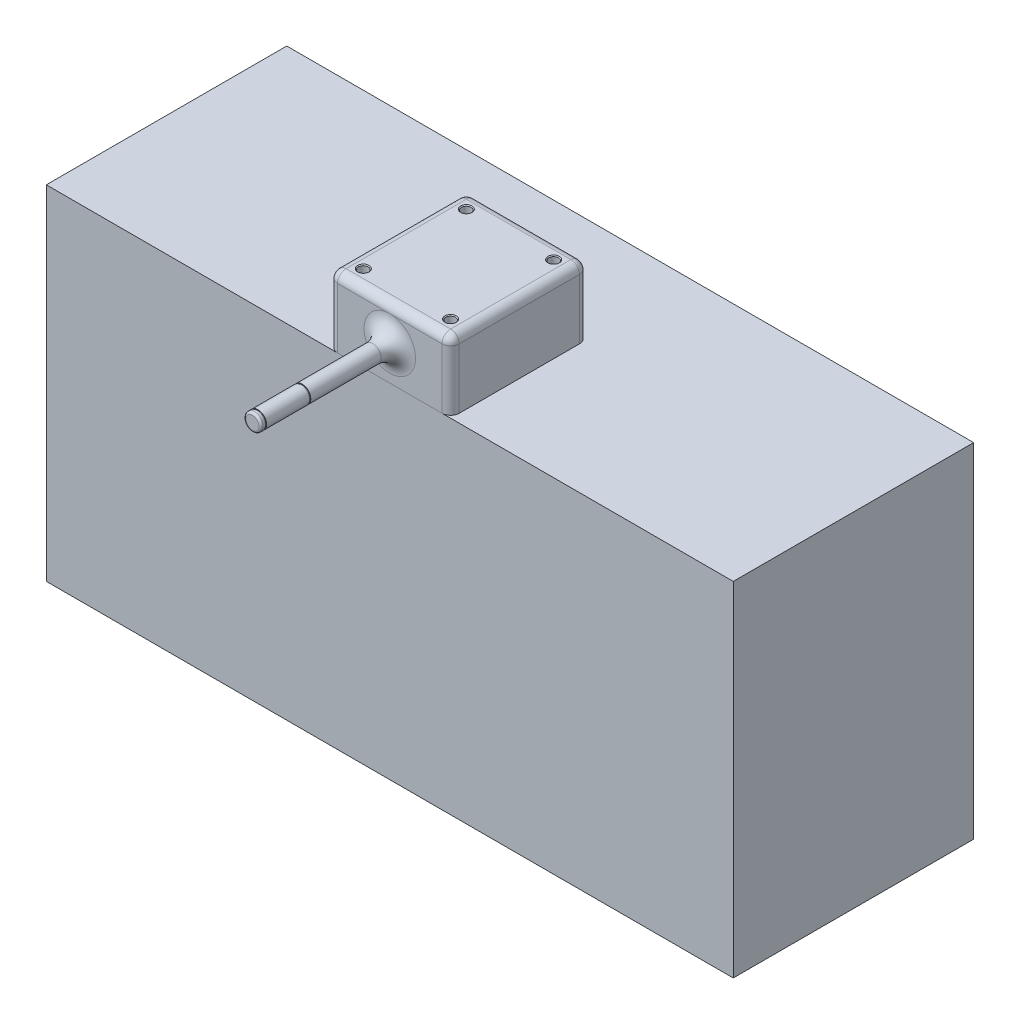
SolidWorks part; units mm, degrees
ref_plane "Front Plane" through (0, 0, 0) normal (0, 0, 1) x (1, 0, 0)
ref_plane "Top Plane" through (0, 0, 0) normal (0, 1, 0) x (1, 0, 0)
ref_plane "Right Plane" through (0, 0, 0) normal (1, 0, 0) x (0, 0, -1)
sketch "Sketch1" plane through (0, 0, 0) normal (0, 0, 1) x (1, 0, 0)
  line L1 (-45, 25.4) -> (45, 25.4)
  line L2 (-45, 25.4) -> (-45, -25.4)
  line L3 (-45, -25.4) -> (45, -25.4)
  line L4 (45, 25.4) -> (45, -25.4)
  line L5 (-45, 25.4) -> (45, -25.4) construction
  line L6 (-45, -25.4) -> (45, 25.4) construction
  circle A0 centre (0, 0) radius 6.35
  point P0 (0, 0)
  dimension "D1" = 12.7
  dimension "D2" = 90
  dimension "D3" = 50.8
extrude "Boss-Extrude1" add sketch "Sketch1" against normal blind 101.6 contours L2 L3 L4 L1
sketch "Sketch10" plane through (0, 0, 0) normal (0, 0, 1) x (1, 0, 0)
  line L0 (-45, -25.4) -> (45, -25.4) construction
  line L1 (-101.6, -25.4) -> (101.6, -25.4)
  line L2 (-101.6, -25.4) -> (-101.6, -228.6)
  line L3 (-101.6, -228.6) -> (101.6, -228.6)
  line L4 (101.6, -25.4) -> (101.6, -228.6)
  point P6 (0, -25.4)
  point P7 (0, -25.4)
  dimension "D1" = 203.2
extrude "Boss-Extrude2" add sketch "Sketch1<3>" along normal blind 101.6 contours A0 region at (0, 0, 0)
sketch "Sketch1<3>" plane through (0, 0, 0) normal (0, 0, 1) x (1, 0, 0) same geometry as "Sketch1"
fillet "Fillet1" radius 6.35 8 edges at (45, 0, 0) (45, 0, -101.6) (-45, 0, -101.6) (-45, 0, 0) (0, 25.4, -101.6) (45, 25.4, -50.8) (0, 25.4, 0) (-45, 25.4, -50.8)
fillet "Fillet2" radius 12.7 1 edges at (6.35, 0, 0)
sketch "Sketch2" plane through (0, 25.4, 0) normal (0, 1, 0) x (1, 0, 0)
  line L0 (-38.65, 50.8) -> (0, 50.8) construction
  line L1 (-32.3, 88.9) -> (32.3, 88.9)
  line L2 (-32.3, 88.9) -> (-32.3, 12.7)
  line L3 (-32.3, 12.7) -> (32.3, 12.7)
  line L4 (32.3, 88.9) -> (32.3, 12.7)
  line L5 (-32.3, 88.9) -> (32.3, 12.7) construction
  line L6 (-32.3, 12.7) -> (32.3, 88.9) construction
  line L7 (-38.65, 95.25) -> (-38.65, 6.35) construction
  line L8 (0, 50.8) -> (0, 6.35) construction
  line L9 (-38.65, 6.35) -> (38.65, 6.35) construction
  line L10 (-32.3, 88.9) -> (-32.3, 95.25) construction
  line L11 (38.65, 95.25) -> (-38.65, 95.25) construction
  line L12 (-32.3, 88.9) -> (-38.65, 88.9) construction
  circle A0 centre (-32.3, 88.9) radius 3.175
  point P0 (0, 50.8)
  dimension "D1" = 6.35
  dimension "D2" = 3.175
hole_wizard "1/4 Clearance Hole1" positions "Sketch3" profile "Sketch4" hole size "1/4" standard "ANSI Inch" end condition through all
sketch "Sketch3" plane through (0, 25.4, 0) normal (0, 1, 0) x (1, 0, 0)
  point P0 (-32.3, 88.9)
  point P3 (-32.3, 12.7)
  point P6 (32.3, 12.7)
  point P9 (32.3, 88.9)
sketch "Sketch4" plane through (-32.3, 25.4, -88.9) normal (1, 0, 0) x (0, 0, 1)
  line L0 (0, 0) -> (0, 50.8)
  line L1 (0, 50.8) -> (3.5687, 50.8)
  line L2 (3.5687, 50.8) -> (3.5687, 0.635)
  line L3 (3.5687, 0.635) -> (4.2037, 0)
  line L5 (4.2037, 0) -> (0, 0)
  line L6 (-3.5687, 0.635) -> (-4.2037, 0) construction
  line L11 (0, -6.35) -> (0, 107.95) construction
  dimension "Thru Hole Dia." = 7.1374
  dimension "Thru Hole Depth" = 50.8
  dimension "Near C'Sink Dia." = 8.4074
  dimension "Near C'Sink Angle" = 90
ref_plane "Plane1" through (0, 6.35, 0) normal (0, 1, 0) x (1, 0, 0)
sketch "Sketch5" plane through (0, 6.35, 0) normal (0, 1, 0) x (1, 0, 0)
  line L0 (-45, -65.7225) -> (45, -65.7225)
  line L1 (-45, -97.4725) -> (45, -97.4725)
  line L2 (-45, -97.4725) -> (-45, -65.7225)
  line L3 (45, -65.7225) -> (45, -97.4725)
  line L4 (-45, -81.5975) -> (0, -81.5975) construction
  line L5 (0, -65.7225) -> (0, -97.4725) construction
  line L6 (0, -101.6) -> (0, -97.4725) construction
  line L7 (-6.35, -101.6) -> (6.35, -101.6) construction
  line L8 (-6.6675, -98.425) -> (0, -97.4725) construction
  line L9 (-6.6675, -97.4725) -> (6.6675, -97.4725)
  line L10 (-6.6675, -97.4725) -> (-6.6675, -98.425)
  line L11 (-6.6675, -98.425) -> (6.6675, -98.425)
  line L12 (6.6675, -97.4725) -> (6.6675, -98.425)
  line L13 (0, -97.4725) -> (6.6675, -98.425) construction
  line L14 (0, -65.7225) -> (6.6675, -64.77) construction
  line L15 (-6.6675, -64.77) -> (0, -65.7225) construction
  line L16 (6.6675, -65.7225) -> (6.6675, -64.77)
  line L17 (-6.6675, -64.77) -> (6.6675, -64.77)
  line L18 (-6.6675, -65.7225) -> (-6.6675, -64.77)
  line L19 (-6.6675, -65.7225) -> (6.6675, -65.7225)
  dimension "D1" = 31.75
  dimension "D2" = 90
  dimension "D3" = 0.9525
  dimension "D4" = 13.335
  dimension "D5" = 3.175
ref_plane "Plane2" through (0, 0, 97.4725) normal (0, 0, 1) x (1, 0, 0)
ref_plane "Plane3" through (0, 0, 65.7225) normal (0, 0, 1) x (1, 0, 0)
sketch "Sketch6" plane through (0, 0, 101.6) normal (0, 0, 1) x (1, 0, 0)
  circle A0 centre (0, 0) radius 5.842
  dimension "D1" = 11.684
sketch "Sketch7" plane through (0, 0, 97.4725) normal (0, 0, 1) x (1, 0, 0)
  circle A1 centre (0, 0) radius 5.842
  circle A2 centre (0, 0) radius 5.842
  circle A3 centre (0, 0) radius 6.35
  circle A4 centre (0, 0) radius 6.35
  dimension "D1" = 0
  dimension "D2" = 0
sketch "Sketch8" plane through (0, 0, 65.7225) normal (0, 0, 1) x (1, 0, 0)
  circle A1 centre (0, 0) radius 5.842
  circle A2 centre (0, 0) radius 5.842
  circle A3 centre (0, 0) radius 6.35
  circle A4 centre (0, 0) radius 6.35
  dimension "D1" = 0
  dimension "D2" = 0
extrude "Cut-Extrude1" cut sketch "Sketch7" along normal up to vertex (0.9525 mm away) contours A4 A2 region at (-6.1704, 0, 97.4725) up to point (6.6675, 6.35, 98.425)
extrude "Cut-Extrude2" cut sketch "Sketch8" against normal up to vertex (0.9525 mm away) contours A4 A2 region at (-6.1704, 0, 65.7225) up to point (-6.6675, 6.35, 64.77)
fillet "Fillet3" radius 1.5875 1 edges at (6.35, 0, 101.6)
sketch "Sketch11" plane through (0, -25.4, 0) normal (0, -1, 0) x (1, 0, 0)
  line L0 (-38.65, 0) -> (38.65, 0) construction
  line L1 (-254, 0) -> (254, 0)
  line L2 (-254, 0) -> (-254, -177.8)
  line L3 (-254, -177.8) -> (254, -177.8)
  line L4 (254, 0) -> (254, -177.8)
  line L5 (-254, 0) -> (254, -177.8) construction
  line L6 (-254, -177.8) -> (254, 0) construction
  line L8 (0, -177.8) -> (0, -101.6) construction
  line L9 (-38.65, -101.6) -> (38.65, -101.6) construction
  point P0 (0, -88.9)
  point P5 (0, -355.9456)
  point P8 (0, -149.5767)
  point P9 (-294.2877, -177.8)
  dimension "D1" = 76.2
  dimension "D2" = 508
extrude "Boss-Extrude3" add sketch "Sketch11" along normal blind 254 separate body
